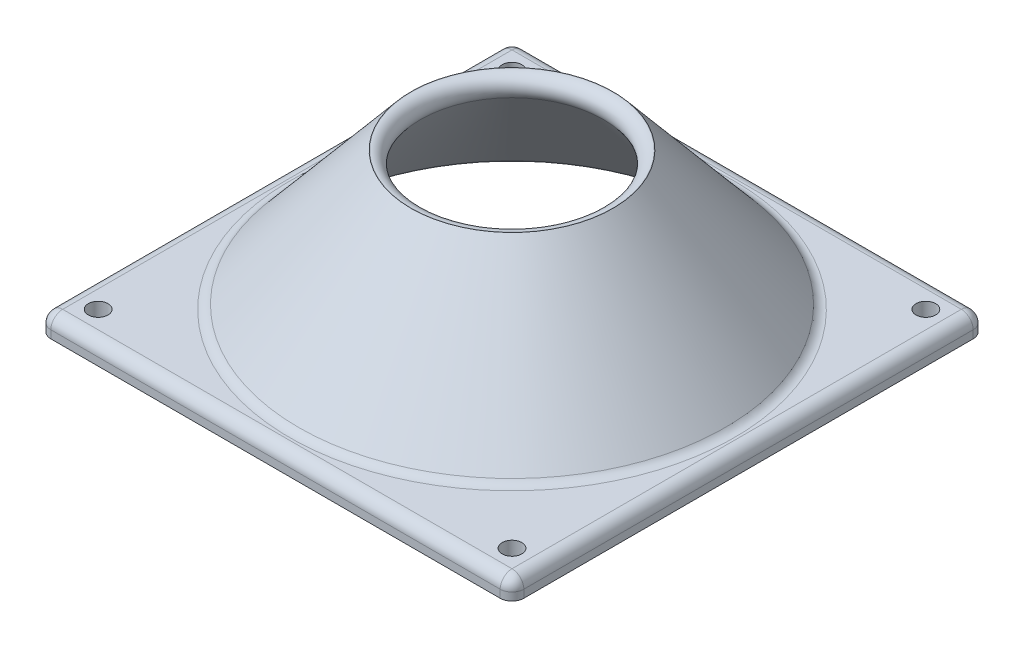
SolidWorks part; units mm, degrees
ref_plane "Front Plane" through (0, 0, 0) normal (0, 0, 1) x (1, 0, 0)
ref_plane "Top Plane" through (0, 0, 0) normal (0, 1, 0) x (1, 0, 0)
ref_plane "Right Plane" through (0, 0, 0) normal (1, 0, 0) x (0, 0, -1)
sketch "Sketch1" plane through (0, 0, 0) normal (0, 1, 0) x (1, 0, 0)
  line L0 (0, -55) -> (0, 55) construction
  line L1 (-60, -60) -> (60, -60)
  line L2 (-60, -60) -> (-60, 60)
  line L3 (-60, 60) -> (60, 60)
  line L4 (60, -60) -> (60, 60)
  line L5 (-60, -60) -> (60, 60) construction
  line L6 (-60, 60) -> (60, -60) construction
  circle A0 centre (-52.5, 52.5) radius 2.5
  circle A1 centre (52.5, 52.5) radius 2.5
  circle A2 centre (52.5, -52.5) radius 2.5
  circle A3 centre (-52.5, -52.5) radius 2.5
  point P0 (0, 0)
  point P19 (0, 0)
  dimension "D3" = 5
  dimension "D1" = 120
  dimension "D2" = 120
  dimension "D4" = 52.5
  dimension "D5" = 4
extrude "Boss-Extrude1" add sketch "Sketch1" along normal blind 5
sketch "Sketch2" plane through (0, 5, 0) normal (0, 1, 0) x (1, 0, 0)
  circle A0 centre (0, 0) radius 55
  dimension "D1" = 110
extrude "Boss-Extrude2" add sketch "Sketch2" along normal blind 35 draft 40
shell "Shell1" thickness 5 removed face at (52.5, 0, 55) removed face at (0, 40, 25.6315)
fillet "Fillet1" radius 3 2 edges at (0, 40, 19.1045) (0, 5, 55)
fillet "Fillet2" radius 3 1 edges at (0, 0, -52.6685)
fillet "Fillet3" radius 3 8 edges at (0, 5, 60) (-60, 5, 0) (0, 5, -60) (60, 5, 0) (60, 2.5, 60) (60, 2.5, -60) (-60, 2.5, -60) (-60, 2.5, 60)
